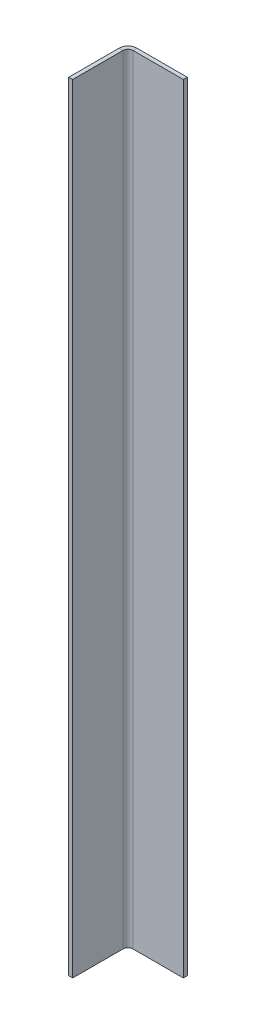
SolidWorks part; units mm, degrees
note: The reader was unsure of these and kept them because the rebuilt part matched: flange length of "Edge-Flange1".
material "AISI 304"
ref_plane "Front" through (0, 0, 0) normal (0, 0, 1) x (1, 0, 0)
ref_plane "Top" through (0, 0, 0) normal (0, 1, 0) x (1, 0, 0)
ref_plane "Right" through (0, 0, 0) normal (1, 0, 0) x (0, 0, -1)
sketch "Sketch1" plane through (0, 0, 0) normal (1, 0, 0) x (0, 0, -1)
  line L1 (-15, -197) -> (15, -197)
  line L2 (-15, -197) -> (-15, 197)
  line L3 (-15, 197) -> (15, 197)
  line L4 (15, -197) -> (15, 197)
  line L5 (-15, -197) -> (15, 197) construction
  line L6 (-15, 197) -> (15, -197) construction
  point P0 (0, 0)
  dimension "D1" = 30
  dimension "D2" = 394
base flange "Base-Flange1" sketch "Sketch1" thickness 2 reverse thickness direction no parameters "D1"=8
edge flange "Edge-Flange1" sketch "Sketch8" flange angle 90 flange length 30 flange position material inside bend radius 2.5 thickness 2 relief rectangular parameters "D6"=10
sketch "Sketch8" plane through (0, 0, -15) normal (0, 0, -1) x (0, 1, 0)
  line L2 (-197, 0) -> (-197, 28)
  line L3 (-197, 28) -> (197, 28)
  line L4 (197, 28) -> (197, 0)
  line L7 (-197, 0) -> (197, 0) construction
  line L8 (-197, 0) -> (197, 0)
bend "EdgeBend1" bend radius 2.5 bend angle 90 parameters "D5"=1
sketch "Bend-Lines1" [suppressed] plane through (0, 0, 0) normal (0, 1, 0) x (1, 0, 0)
sketch "Bounding-Box1" [suppressed] plane through (0, 0, 0) normal (0, 1, 0) x (1, 0, 0)
sheet metal parameters "Sheet-Metal1" thickness 2 parameters "D1"=8
flat pattern "Flat-Pattern1" [suppressed]
sketch "Bend-Lines2" plane through (0, 0, 0) normal (0, 1, 0) x (1, 0, 0)
sketch3d "Bounding-Box2" [suppressed]
  line L0 (15, 191, 0) -> (15, -191, 0) construction
  line L1 (-15, 191, 0) -> (-15, -191, 0) construction
  line L2 (15, 191, 0) -> (-15, 191, 0) construction
  line L3 (15, -191, 0) -> (-15, -191, 0) construction
sheet metal parameters "Sheet-Metal2" thickness 2 parameters "D1"=8
flat pattern "Flat-Pattern1"
sketch "Bend-Lines2" plane through (0, 0, 0) normal (1, 0, 0) x (0, 0, -1)
  line L0 (13.2489, -197) -> (13.2489, 197) construction
  line L1 (13.2489, -197) -> (13.2489, 197) construction
sketch3d "Bounding-Box2" [suppressed]
  line L0 (-15, 197, 0) -> (-15, -197, 0) construction
  line L1 (41.4978, 197, 0) -> (41.4978, -197, 0) construction
  line L2 (-15, 197, 0) -> (41.4978, 197, 0) construction
  line L3 (-15, -197, 0) -> (41.4978, -197, 0) construction
bend of the flat pattern "Flatten-<EdgeBend1>1"
